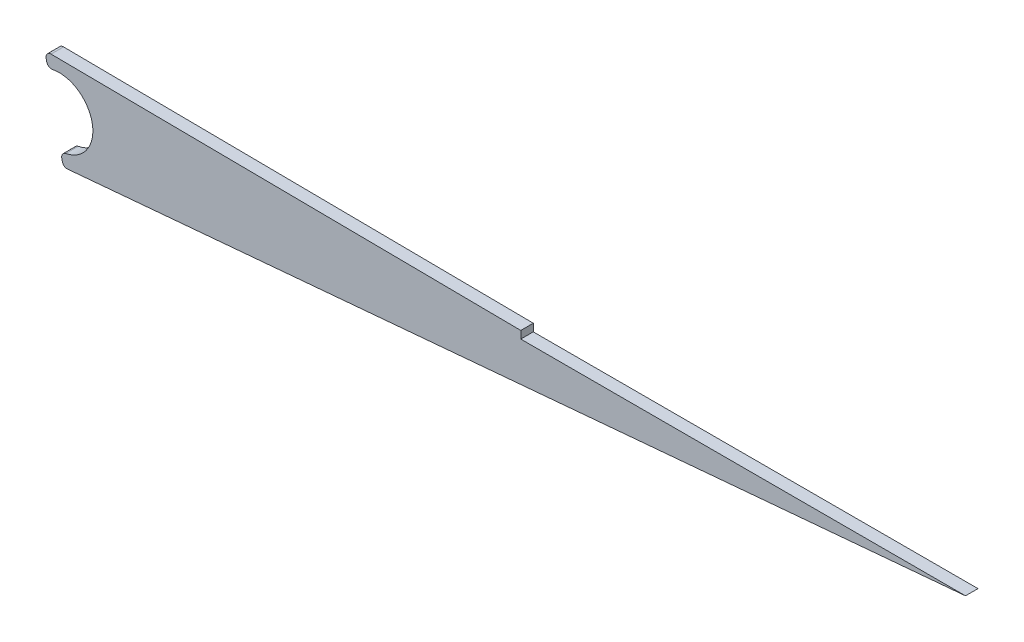
SolidWorks part; units mm, degrees
material "AISI 1020"
ref_plane "Спереди" through (0, 0, 0) normal (0, 0, 1) x (1, 0, 0)
ref_plane "Сверху" through (0, 0, 0) normal (0, 1, 0) x (1, 0, 0)
ref_plane "Справа" through (0, 0, 0) normal (1, 0, 0) x (0, 0, -1)
sketch "Эскиз1" plane through (0, 0, 0) normal (0, 0, 1) x (1, 0, 0)
  line L0 (1.2792, -33.1689) -> (1.0646, -32.0929) construction
  line L1 (-4.9978, -1.6914) -> (-5.2123, -0.6154) construction
  line L2 (1.2792, -33.1689) -> (1.0646, -32.0929)
  line L3 (-4.9978, -1.6914) -> (-5.2123, -0.6154)
  line L4 (362.5978, -3) -> (3.4168, -34.77) construction
  line L5 (362.5978, -3) -> (3.4168, -34.77)
  line L6 (184.686, 0) -> (184.686, -3) construction
  line L7 (184.686, 0) -> (184.686, -3)
  line L8 (362.5978, -3) -> (184.686, -3)
  line L9 (184.686, 0) -> (-3.232, 1.7756)
  arc A0 (2.6356, -29.7402) -> (1.0646, -32.0929) centre (3.026, -31.7018) ccw construction
  arc A1 (-4.9978, -1.6914) -> (-2.6446, -3.2616) centre (-3.0364, -1.3003) ccw construction
  arc A2 (2.6356, -29.7402) -> (1.0646, -32.0929) centre (3.026, -31.7018) ccw
  arc A3 (-4.9978, -1.6914) -> (-2.6446, -3.2616) centre (-3.0364, -1.3003) ccw
  arc A4 (2.6356, -29.7402) -> (-2.6446, -3.2616) centre (0, -16.5) ccw construction
  arc A5 (2.6356, -29.7402) -> (-2.6446, -3.2616) centre (0, -16.5) ccw
  arc A6 (1.2792, -33.1689) -> (3.4168, -34.77) centre (3.2406, -32.7778) ccw construction
  arc A7 (1.2792, -33.1689) -> (3.4168, -34.77) centre (3.2406, -32.7778) ccw
  arc A8 (-3.232, 1.7756) -> (-5.2123, -0.6154) centre (-3.2509, -0.2243) ccw
  arc A9 (-3.8524, 1.6831) -> (-5.2123, -0.6154) centre (-3.2509, -0.2243) ccw construction
base flange "Базовая кромка1" sketch "Эскиз1" thickness 5 reverse thickness direction no parameters "D1"=0.74
sketch "Сгиб-Линии1" [suppressed] plane through (0, 0, 0) normal (0, 1, 0) x (1, 0, 0)
sketch "Граничная рамка1" [suppressed] plane through (0, 0, 0) normal (0, 1, 0) x (1, 0, 0)
sheet metal parameters "Листовой металл3" thickness 5 parameters "D1"=0.74
flat pattern "Развертка3" [suppressed]
sketch "Сгиб-Линии2" plane through (0, 0, 0) normal (0, 1, 0) x (1, 0, 0)
sketch3d "Граничная рамка2" [suppressed]
  line L0 (-5.2315, 18.2946, 0) -> (362.6103, 14.8188, 0) construction
  line L1 (-5.5763, -18.1944, 0) -> (362.2655, -21.6702, 0) construction
  line L2 (-5.2315, 18.2946, 0) -> (-5.5763, -18.1944, 0) construction
  line L3 (362.6103, 14.8188, 0) -> (362.2655, -21.6702, 0) construction
